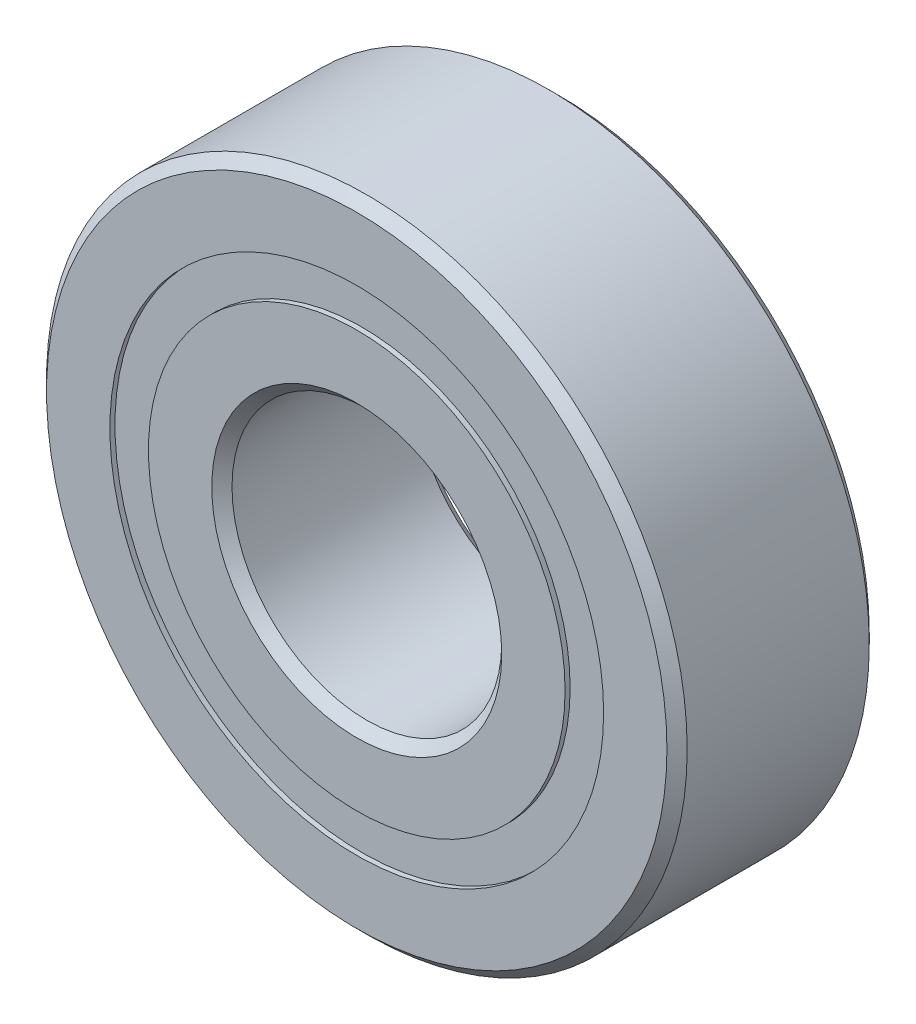
SolidWorks part; units mm, degrees
ref_plane "Front Plane" through (0, 0, 0) normal (0, 0, 1) x (1, 0, 0)
ref_plane "Top Plane" through (0, 0, 0) normal (0, 1, 0) x (1, 0, 0)
ref_plane "Right Plane" through (0, 0, 0) normal (1, 0, 0) x (0, 0, -1)
sketch "Sketch1" plane through (0, 0, 0) normal (1, 0, 0) x (0, 0, -1)
  line L0 (-3, 0) -> (3, 0) construction
  line L1 (0, 9.5) -> (0, -9.5) construction
  line L2 (2.7, 9.5) -> (-2.7, 9.5)
  line L3 (-2.7, 9.5) -> (-3, 9.2)
  line L4 (-3, 9.2) -> (-3, 7.3214)
  line L5 (-3, 7.3214) -> (-1.3333, 7.3214)
  line L6 (3, 7.3214) -> (1.3333, 7.3214)
  line L7 (3, 9.2) -> (3, 7.3214)
  line L8 (2.7, 9.5) -> (3, 9.2)
  line L9 (0, 9.5) -> (0, 6.75) construction
  line L10 (0, 6.75) -> (0, 4) construction
  arc A0 (-1.3333, 7.3214) -> (1.3333, 7.3214) centre (0, 6.75) cw
  point P14 (0, 4)
  dimension "Width" = 6
  dimension "OD" = 19
  dimension "D1" = 45
  dimension "D2" = 0.3
  dimension "Shaft Dia" = 8
  dimension "D3" = 2.6667
  dimension "D4" = 0.5714
revolve "Revolve1" add sketch "Sketch1" angle 360 about L0
sketch "Sketch3" plane through (0, 0, 0) normal (1, 0, 0) x (0, 0, -1)
  line L0 (-3, 6.1786) -> (-1.3333, 6.1786)
  line L1 (0, 9.5) -> (0, -9.5) construction
  line L2 (-3, 9.2) -> (-3, 7.3214) construction
  line L3 (-3, 6.1786) -> (-3, 4.3)
  line L4 (-2.7, 9.5) -> (-3, 9.2) construction
  line L5 (-3, 4.3) -> (-2.7, 4)
  line L6 (-2.7, 4) -> (2.7, 4)
  line L7 (2.7, 9.5) -> (2.7, -9.5) construction
  line L8 (2.7, 4) -> (3, 4.3)
  line L9 (3, -9.2) -> (3, 9.2) construction
  line L10 (3, 4.3) -> (3, 6.1786)
  line L11 (3, 6.1786) -> (1.3333, 6.1786)
  line L13 (2.7, 9.5) -> (3, 9.2) construction
  arc A0 (1.3333, 7.3214) -> (-1.3333, 7.3214) centre (0, 6.75) ccw construction
  arc A1 (1.3333, 6.1786) -> (-1.3333, 6.1786) centre (0, 6.75) cw
revolve "Revolve3" add sketch "Sketch3" angle 360 about L0
sketch "Sketch4" plane through (0, 0, 0) normal (1, 0, 0) x (0, 0, -1)
  line L0 (-1.4506, 6.75) -> (1.4506, 6.75)
  arc A2 (-1.4506, 6.75) -> (1.4506, 6.75) centre (0, 6.75) cw
  arc A3 (1.3333, 7.3214) -> (-1.3333, 7.3214) centre (0, 6.75) ccw construction
revolve "Revolve4" add sketch "Sketch4" angle 360 about L0
ref_axis "Axis1" through (0, 0, -3) along (0, 0, 1)
pattern_circular "CirPattern1" count 12 every 30 about axis through (0, 0, -3) along (0, 0, 1) of bodies 104
sketch "Sketch5" plane through (0, 0, 0) normal (1, 0, 0) x (0, 0, -1)
  line L0 (-3, 7.3214) -> (-1.3333, 7.3214) construction
  line L1 (-2.85, 7.3214) -> (-1.4506, 7.3214)
  line L2 (-2.85, 7.3214) -> (-2.85, 6.1786)
  line L3 (-2.85, 6.1786) -> (-1.4506, 6.1786)
  line L4 (-1.4506, 7.3214) -> (-1.4506, 6.1786)
  line L5 (-3, 6.1786) -> (-1.3333, 6.1786) construction
  line L6 (3, 7.3214) -> (1.3333, 7.3214) construction
  line L7 (2.85, 7.3214) -> (1.4506, 7.3214)
  line L8 (2.85, 7.3214) -> (2.85, 6.1786)
  line L9 (2.85, 6.1786) -> (1.4506, 6.1786)
  line L10 (1.4506, 7.3214) -> (1.4506, 6.1786)
  line L11 (3, 6.1786) -> (1.3333, 6.1786) construction
  line L12 (-2.7, 9.5) -> (-3, 9.2) construction
  point P18 (-2.85, 9.35)
revolve "Revolve5" add sketch "Sketch5" angle 360 about L0
sketch "Sketch6" plane through (0, 0, 0) normal (1, 0, 0) x (0, 0, -1)
  line L0 (3, 0) -> (-3, 0) construction
  line L1 (3, 7.3214) -> (1.9, 7.3214)
  line L2 (3, 7.3214) -> (3, 9.5)
  line L3 (3, 9.5) -> (1.9, 9.5)
  line L4 (1.9, 7.3214) -> (1.9, 9.5)
  dimension "Th" = 1.1
  dimension "Flange OD" = 19
revolve "Revolve6" [suppressed] add sketch "Sketch6" angle 360 about L0
equation "\"D2@Sketch1\" = \"Width@Sketch1\"*.05"
equation "\"D3@Sketch1\" = \"Width@Sketch1\"/2.25"
equation "\"D4@Sketch1\" = (((\"OD@Sketch1\"-\"Width@Sketch1\")/2)/3.25)/3.5"
equation "\"D2@CirPattern1\" = 360/\"Balls@CirPattern1\""
